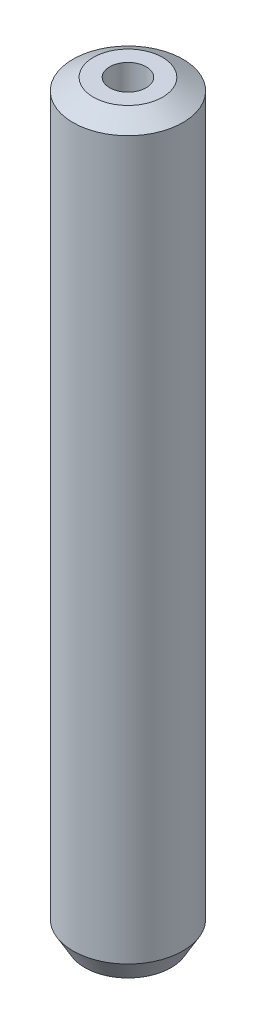
SolidWorks part; units mm, degrees
ref_plane "Front Plane" through (0, 0, 0) normal (0, 0, 1) x (1, 0, 0)
ref_plane "Top Plane" through (0, 0, 0) normal (0, 1, 0) x (1, 0, 0)
ref_plane "Right Plane" through (0, 0, 0) normal (1, 0, 0) x (0, 0, -1)
sketch "Sketch1" plane through (0, 0, 0) normal (0, 1, 0) x (1, 0, 0)
  circle A0 centre (0, 0) radius 15
  dimension "SHAFT_OD" = 30
extrude "Boss-Extrude1" add sketch "Sketch1" along normal blind 204.6059
sketch "Sketch2" plane through (0, 0, 0) normal (0, 1, 0) x (1, 0, 0)
  circle A0 centre (0, 0) radius 4.9778
  dimension "BORE_D" = 9.9556
extrude "Cut-Extrude1" cut sketch "Sketch2" along normal through all
chamfer "Chamfer1" distance 3.2139 angle 60 2 edges at (0, 204.6059, 15) (0, 0, 15) first distance on face at (0, 204.6059, 15) first distance on face at (0, 0, 4.9778)
